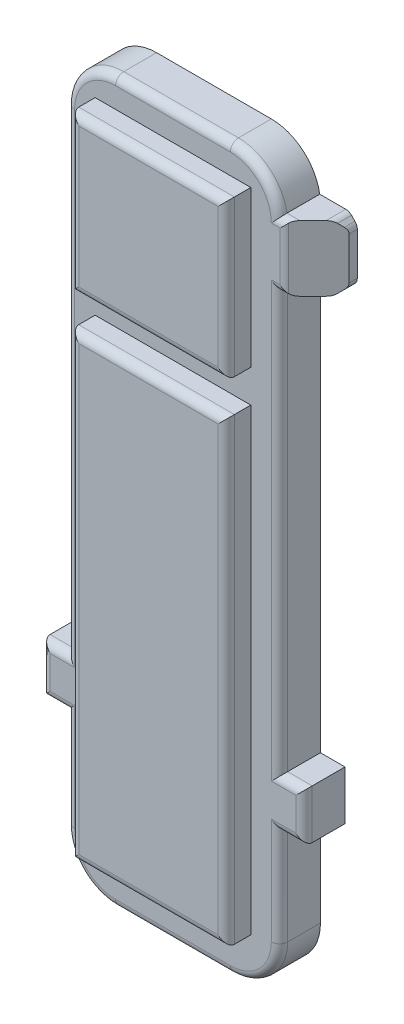
SolidWorks part; units mm, degrees
ref_plane "Front Plane" through (0, 0, 0) normal (0, 0, 1) x (1, 0, 0)
ref_plane "Top Plane" through (0, 0, 0) normal (0, 1, 0) x (1, 0, 0)
ref_plane "Right Plane" through (0, 0, 0) normal (1, 0, 0) x (0, 0, -1)
sketch "Sketch1" plane through (0, 0, 0) normal (0, 0, 1) x (1, 0, 0)
  line L0 (-5, 10) -> (5, 10) construction
  line L1 (-6.5, -20) -> (6.5, -20) construction
  line L2 (-6.5, -20) -> (-6.5, 20) construction
  line L3 (-6.5, 20) -> (6.5, 20) construction
  line L4 (6.5, -20) -> (6.5, 20) construction
  line L5 (-6.5, -20) -> (6.5, 20) construction
  line L6 (-6.5, 20) -> (6.5, -20) construction
  line L7 (-5, -20) -> (5, -20) construction
  line L8 (-5, -20) -> (-5, 8.5) construction
  line L9 (-5, 20) -> (5, 20) construction
  line L10 (5, -20) -> (5, 8.5) construction
  line L11 (-5, -20) -> (5, 20) construction
  line L12 (-5, 20) -> (5, -20) construction
  line L13 (-5, 8.5) -> (5, 8.5) construction
  line L14 (-5, 10) -> (-5, 20) construction
  line L15 (5, 10) -> (5, 20) construction
  line L16 (-4.75, 19.75) -> (4.75, 19.75)
  line L17 (4.75, 10.25) -> (4.75, 19.75)
  line L18 (-4.75, 10.25) -> (4.75, 10.25)
  line L19 (-4.75, 10.25) -> (-4.75, 19.75)
  line L20 (-4.75, -19.75) -> (4.75, -19.75)
  line L21 (4.75, -19.75) -> (4.75, 8.25)
  line L22 (-4.75, 8.25) -> (4.75, 8.25)
  line L23 (-4.75, -19.75) -> (-4.75, 8.25)
  point P0 (0, 0)
  point P5 (0, 0)
  dimension "D1" = 40
  dimension "D2" = 13
  dimension "D3" = 40
  dimension "D4" = 10
  dimension "D5" = 1.5
  dimension "D6" = 10
  dimension "D7" = 0.25
  dimension "D8" = 0.25
extrude "Boss-Extrude1" add sketch "Sketch1" along normal blind 2.5
sketch "Sketch2" plane through (0, 0, 0) normal (0, 0, 1) x (1, 0, 0)
  line L0 (-5, 10) -> (5, 10) construction
  line L1 (-6.5, -22.5) -> (6.5, -22.5)
  line L2 (-6.5, -22.5) -> (-6.5, 21.5)
  line L3 (-6.5, 21.5) -> (6.5, 21.5)
  line L4 (6.5, -22.5) -> (6.5, 21.5)
  line L5 (-6.5, -22.5) -> (6.5, 21.5) construction
  line L6 (-6.5, 21.5) -> (6.5, -22.5) construction
  line L7 (-5, -20) -> (5, -20) construction
  line L8 (-5, -20) -> (-5, 8.5) construction
  line L9 (-5, 20) -> (5, 20) construction
  line L10 (5, -20) -> (5, 8.5) construction
  line L11 (-5, -20) -> (5, 20) construction
  line L12 (-5, 20) -> (5, -20) construction
  line L13 (-5, 8.5) -> (5, 8.5) construction
  line L14 (-5, 10) -> (-5, 20) construction
  line L15 (5, 10) -> (5, 20) construction
  line L16 (-5.25, 20.25) -> (5.25, 20.25) construction
  line L17 (5.25, 9.75) -> (5.25, 20.25) construction
  line L18 (-5.25, 9.75) -> (5.25, 9.75) construction
  line L19 (-5.25, 9.75) -> (-5.25, 20.25) construction
  line L20 (-4.75, -19.75) -> (4.75, -19.75) construction
  line L21 (4.75, -19.75) -> (4.75, 8.25) construction
  line L22 (-4.75, 8.25) -> (4.75, 8.25) construction
  line L23 (-4.75, -19.75) -> (-4.75, 8.25) construction
  point P0 (0, -0.5)
  point P5 (0, 0)
  dimension "D1" = 44
  dimension "D2" = 13
  dimension "D3" = 40
  dimension "D4" = 10
  dimension "D5" = 1.5
  dimension "D6" = 10
  dimension "D7" = 0.25
  dimension "D8" = 0.25
extrude "Boss-Extrude2" add sketch "Sketch2" along normal blind 1 and the other way blind 1.5
fillet "Fillet3" radius 0.5 4 edges at (0, 19.75, 2.5) (4.75, 15, 2.5) (0, 10.25, 2.5) (-4.75, 15, 2.5)
fillet "Fillet7" radius 0.5 4 edges at (0, 8.25, 2.5) (4.75, -5.75, 2.5) (0, -19.75, 2.5) (-4.75, -5.75, 2.5)
fillet "Fillet11" radius 3 4 edges at (-6.5, 21.5, -0.25) (6.5, 21.5, -0.25) (6.5, -22.5, -0.25) (-6.5, -22.5, -0.25)
sketch "Sketch3" plane through (0, 0, -1.5) normal (0, 0, -1) x (-1, 0, 0)
  line L1 (-8.75, 19) -> (-4.75, 19)
  line L2 (-8.75, 19) -> (-8.75, 15)
  line L3 (-8.75, 15) -> (-4.75, 15)
  line L4 (-4.75, 19) -> (-4.75, 15)
  line L5 (-8.75, 19) -> (-4.75, 15) construction
  line L6 (-8.75, 15) -> (-4.75, 19) construction
  point P0 (-6.75, 17)
  dimension "D1" = 17
  dimension "D2" = 4
  dimension "D3" = 4
  dimension "D4" = 6.75
extrude "Boss-Extrude3" add sketch "Sketch3" against normal up to surface (2.5 mm away) up to face at (0, -5.75, 1)
chamfer "Chamfer1" distance 2 angle 45 1 edges at (8.75, 17, 1)
chamfer "Chamfer2" distance 0.5 angle 45 2 edges at (8.75, 19, -1.25) (8.75, 15, -1.25)
sketch "Sketch4" plane through (0, 0, -1.5) normal (0, 0, -1) x (-1, 0, 0)
  line L1 (-8, -13.5) -> (8, -13.5)
  line L2 (-8, -13.5) -> (-8, -10.5)
  line L3 (-8, -10.5) -> (8, -10.5)
  line L4 (8, -13.5) -> (8, -10.5)
  line L5 (-8, -13.5) -> (8, -10.5) construction
  line L6 (-8, -10.5) -> (8, -13.5) construction
  point P0 (0, -12)
  dimension "D1" = 12
  dimension "D2" = 3
  dimension "D3" = 16
extrude "Boss-Extrude4" add sketch "Sketch4" against normal up to surface (2.5 mm away) up to face at (0, 15, 1)
fillet "Fillet19" radius 0.5 10 edges at (6.5, -16.5, 1) (5.6213, -21.6213, 1) (0, -22.5, 1) (-5.6213, -21.6213, 1) (-6.5, -16.5, 1) (-6.5, 4, 1) (-5.6213, 20.6213, 1) (0, 21.5, 1) (5.4365, 20.7913, 1) (6.5, 2.25, 1)
fillet "Fillet18" radius 0.5 13 edges at (8.25, 19, -1) (8.75, 18.5, -1.25) (8.75, 15.5, -1.25) (8.25, 15, -1) (6.75, 17, 1) (-7, -13.5, 1) (-8, -12, 1) (-7, -10.5, 1) (6.3497, 19, 1) (6.375, 15, 1) (8, -12, 1) (7, -13.5, 1) (7, -10.5, 1)
